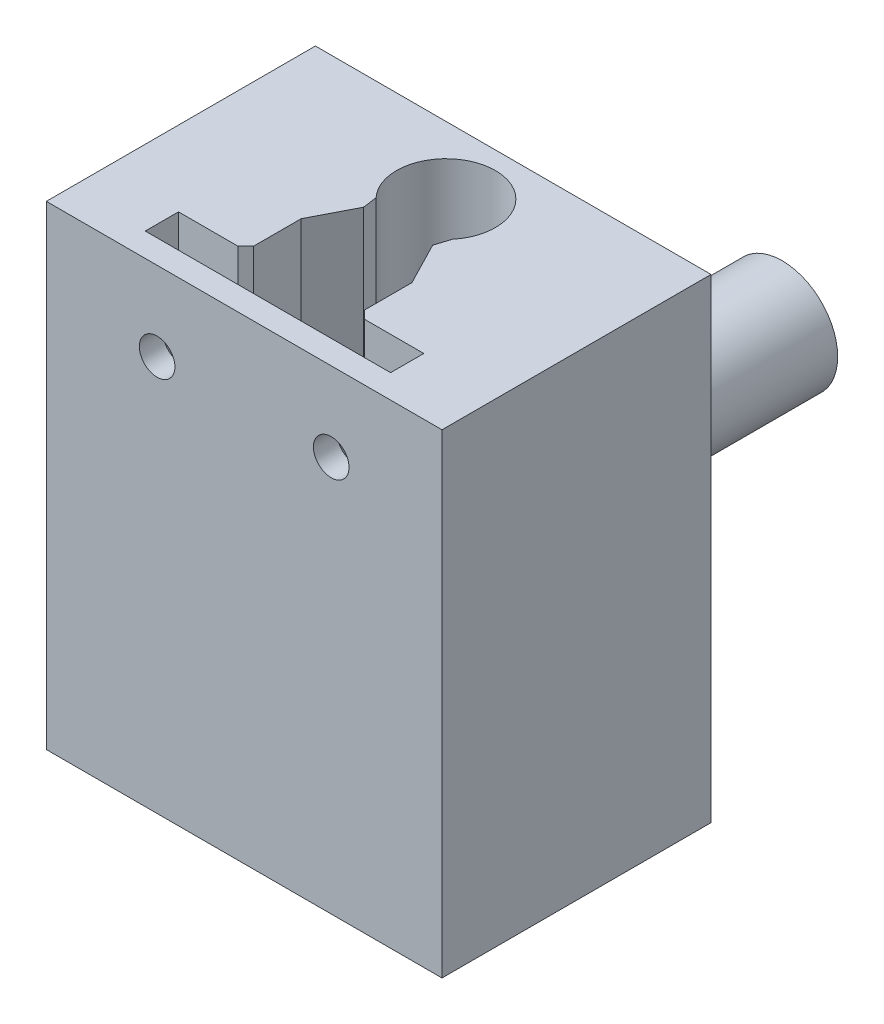
SolidWorks part; units mm, degrees
ref_plane "Front Plane" through (0, 0, 0) normal (0, 0, 1) x (1, 0, 0)
ref_plane "Top Plane" through (0, 0, 0) normal (0, 1, 0) x (1, 0, 0)
ref_plane "Right Plane" through (0, 0, 0) normal (1, 0, 0) x (0, 0, -1)
sketch "Sketch1" plane through (0, 0, 0) normal (0, 1, 0) x (1, 0, 0)
  line L1 (25, -17) -> (-25, -17)
  line L2 (25, -17) -> (25, 17)
  line L3 (25, 17) -> (-25, 17)
  line L4 (-25, -17) -> (-25, 17)
  line L5 (25, -17) -> (-25, 17) construction
  line L6 (25, 17) -> (-25, -17) construction
  point P0 (0, 0)
  dimension "D1" = 50
  dimension "D2" = 34
extrude "Boss-Extrude1" add sketch "Sketch1" along normal blind 60
sketch "Sketch2" plane through (0, 60, 0) normal (0, 1, 0) x (1, 0, 0)
  line L0 (-3.75, 3.5) -> (-7, -2.8)
  line L1 (15.5, -14) -> (-15.5, -14)
  line L2 (15.5, -14) -> (15.5, -9.8)
  line L3 (15.5, -9.8) -> (7, -9.8)
  line L4 (-15.5, -14) -> (-15.5, -9.8)
  line L5 (15.5, -14) -> (-15.5, -9.8) construction
  line L6 (15.5, -9.8) -> (-15.5, -14) construction
  line L7 (-7, -2.8) -> (-7, -9.8)
  line L8 (3.75, 3.5) -> (7, -2.8)
  line L9 (7, -2.8) -> (7, -9.8)
  line L10 (0, -1000) -> (0, 49000) construction
  line L11 (-25, -17) -> (25, -17) construction
  line L12 (-7, -9.8) -> (-15.5, -9.8)
  arc A0 (3.75, 3.5) -> (-3.75, 3.5) centre (0, 8.5) ccw
  point P2 (0, -11.9)
  dimension "D1" = 12.5
  dimension "D6" = 22.5
  dimension "D2" = 4.2
  dimension "D3" = 31
  dimension "D4" = 7
  dimension "D5" = 7.5
  dimension "D7" = 14
  dimension "D8" = 3
extrude "Cut-Extrude1" cut sketch "Sketch2" against normal through all
sketch "Sketch3" plane through (0, 0, 17) normal (0, 0, 1) x (1, 0, 0)
  line L0 (0, -1000) -> (0, 49000) construction
  line L2 (-25, 0) -> (25, 0) construction
  circle A0 centre (-11, 50) radius 2.25
  circle A1 centre (11, 50) radius 2.25
  dimension "D1" = 4.5
  dimension "D3" = 50
  dimension "D2" = 22
extrude "Cut-Extrude2" cut sketch "Sketch3" against normal through all
sketch "Sketch4" plane through (0, 0, -17) normal (0, 0, -1) x (-1, 0, 0)
  line L1 (14.75, 52.1651) -> (11, 54.3301)
  line L2 (11, 54.3301) -> (7.25, 52.1651)
  line L3 (7.25, 52.1651) -> (7.25, 47.8349)
  line L4 (7.25, 47.8349) -> (11, 45.6699)
  line L5 (11, 45.6699) -> (14.75, 47.8349)
  line L6 (14.75, 47.8349) -> (14.75, 52.1651)
  line L7 (-7.25, 47.8349) -> (-7.25, 52.1651)
  line L8 (-7.25, 52.1651) -> (-11, 54.3301)
  line L9 (-11, 54.3301) -> (-14.75, 52.1651)
  line L10 (-14.75, 52.1651) -> (-14.75, 47.8349)
  line L11 (-14.75, 47.8349) -> (-11, 45.6699)
  line L12 (-11, 45.6699) -> (-7.25, 47.8349)
  circle A0 centre (11, 50) radius 3.75 construction
  circle A1 centre (-11, 50) radius 3.75 construction
  dimension "D1" = 7.5
extrude "Cut-Extrude3" cut sketch "Sketch4" against normal offset from surface (24.8 mm away) 2 up to face at (-13.25, 50, 9.8)
chamfer "Chamfer1" distance 1 angle 45 4 edges at (7, 30, 9.8) (-7, 30, 9.8) (-3.75, 30, -3.5) (3.75, 30, -3.5) first distance on face at (8.75, 50, 9.8) first distance on face at (-7, 30, 6.3) first distance on face at (0, 30, -9.125) first distance on face at (5.375, 30, -0.35)
sketch "Sketch5" plane through (0, 0, -17) normal (0, 0, -1) x (-1, 0, 0)
  circle A0 centre (0, 25) radius 7
  point P2 (0, 23.0938)
  dimension "D2" = 14
  dimension "D1" = 25
extrude "Boss-Extrude2" add sketch "Sketch5" along normal blind 14
sketch "Sketch6" plane through (0, 0, -31) normal (0, 0, -1) x (-1, 0, 0)
  circle A0 centre (0, 25) radius 4.15
  circle A1 centre (0, 25) radius 7
  dimension "D1" = 8.3
  dimension "D2" = 14
extrude "Boss-Extrude3" add sketch "Sketch6" along normal blind 20
chamfer "Chamfer2" distance 10 angle 1 1 edges at (-4.15, 25, -31) first distance on face at (-4.15, 25, -51)
chamfer "Chamfer4" distance 10 angle 45 1 edges at (7, 25, -17)
